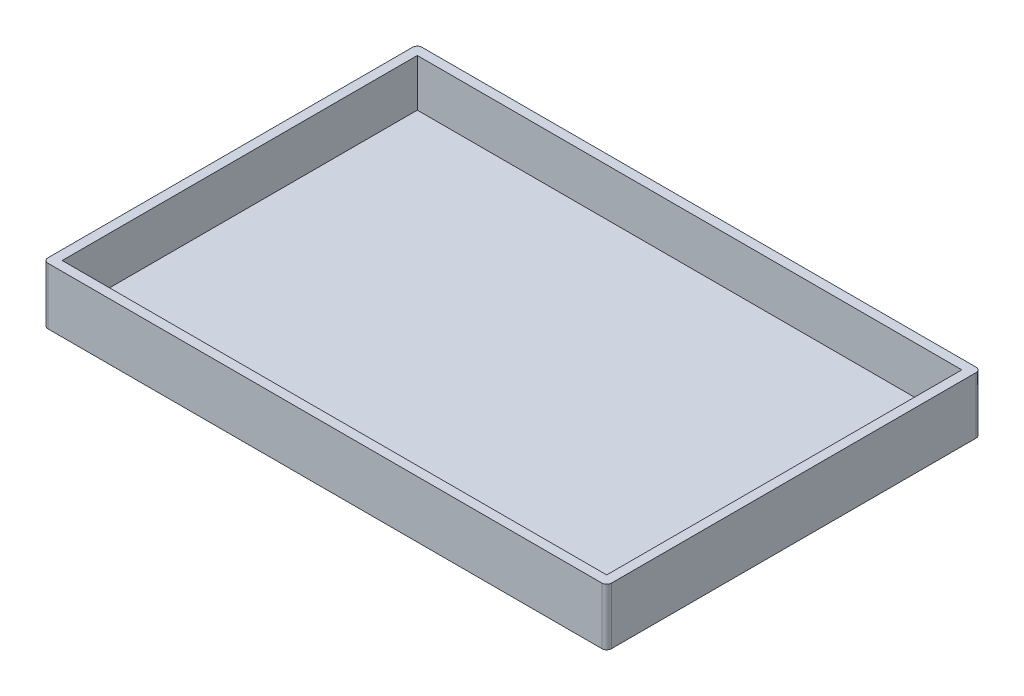
SolidWorks part; units mm, degrees
ref_plane "Front Plane" through (0, 0, 0) normal (0, 0, 1) x (1, 0, 0)
ref_plane "Top Plane" through (0, 0, 0) normal (0, 1, 0) x (1, 0, 0)
ref_plane "Right Plane" through (0, 0, 0) normal (1, 0, 0) x (0, 0, -1)
sketch "Sketch1" plane through (0, 0, 0) normal (0, 1, 0) x (1, 0, 0)
  line L1 (-57.5, -37.5) -> (57.5, -37.5)
  line L2 (-57.5, -37.5) -> (-57.5, 37.5)
  line L3 (-57.5, 37.5) -> (57.5, 37.5)
  line L4 (57.5, -37.5) -> (57.5, 37.5)
  line L5 (-57.5, -37.5) -> (57.5, 37.5) construction
  line L6 (-57.5, 37.5) -> (57.5, -37.5) construction
  point P0 (0, 0)
  dimension "D1" = 75
  dimension "D2" = 115
extrude "Boss-Extrude1" add sketch "Sketch1" along normal blind 10
shell "Shell1" thickness 2 removed face at (0, 10, 0) outward yes
fillet "Fillet1" radius 1 4 edges at (-59.5, 4, -39.5) (59.5, 4, 39.5) (59.5, 4, -39.5) (-59.5, 4, 39.5)
